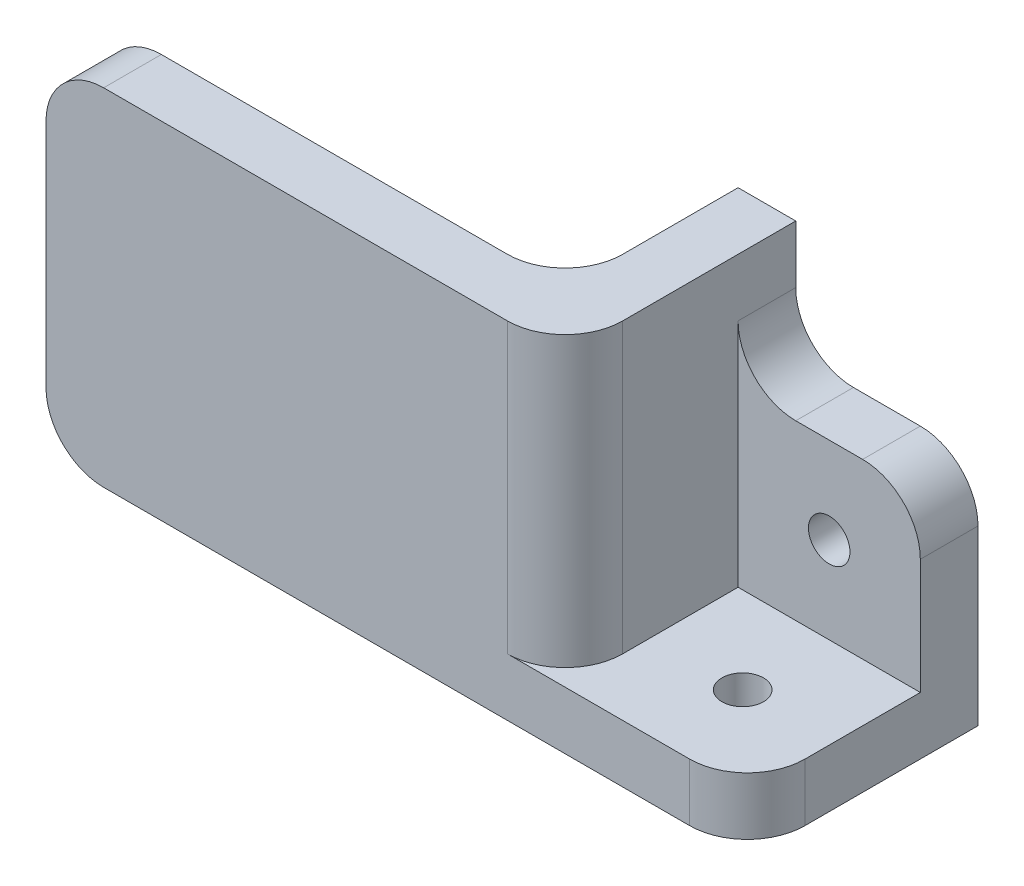
SolidWorks part; units mm, degrees
ref_plane "Front" through (0, 0, 0) normal (0, 0, 1) x (1, 0, 0)
ref_plane "Top" through (0, 0, 0) normal (0, 1, 0) x (1, 0, 0)
ref_plane "Right" through (0, 0, 0) normal (1, 0, 0) x (0, 0, -1)
sketch "Sketch1" plane through (0, 0, 0) normal (0, 1, 0) x (1, 0, 0)
  line L1 (-10.033, -12.7) -> (10.033, -12.7)
  line L2 (-10.033, -12.7) -> (-10.033, 12.7)
  line L3 (-10.033, 12.7) -> (10.033, 12.7)
  line L4 (10.033, -12.7) -> (10.033, 12.7)
  line L5 (-10.033, -12.7) -> (10.033, 12.7) construction
  line L6 (-10.033, 12.7) -> (10.033, -12.7) construction
  point P0 (0, 0)
  dimension "D1" = 20.066
  dimension "D2" = 25.4
extrude "Boss-Extrude1" add sketch "Sketch1" along normal blind 6.35
sketch "Sketch2" plane through (0, 0, -12.7) normal (0, 0, -1) x (-1, 0, 0)
  line L1 (-10.033, 0) -> (10.033, 0)
  line L2 (-10.033, 0) -> (-10.033, 25.4)
  line L3 (-10.033, 25.4) -> (10.033, 25.4)
  line L4 (10.033, 0) -> (10.033, 25.4)
  point P5 (10.033, 0)
  dimension "D1" = 25.4
extrude "Boss-Extrude2" add sketch "Sketch2" against normal blind 6.35
sketch "Sketch3" plane through (-10.033, 0, 0) normal (-1, 0, 0) x (0, 0, 1)
  line L1 (-12.7, 0) -> (12.7, 0)
  line L2 (-12.7, 0) -> (-12.7, 38.1)
  line L3 (-12.7, 38.1) -> (12.7, 38.1)
  line L4 (12.7, 0) -> (12.7, 38.1)
  point P5 (12.7, 0)
  dimension "D1" = 38.1
extrude "Boss-Extrude3" add sketch "Sketch3" along normal blind 6.35
sketch "Sketch4" plane through (0, 0, 12.7) normal (0, 0, 1) x (1, 0, 0)
  line L1 (-16.383, 38.1) -> (-67.183, 38.1)
  line L2 (-16.383, 38.1) -> (-16.383, 0)
  line L3 (-16.383, 0) -> (-67.183, 0)
  line L4 (-67.183, 38.1) -> (-67.183, 0)
  point P5 (-16.383, 0)
  dimension "D1" = 50.8
extrude "Boss-Extrude4" add sketch "Sketch4" against normal blind 6.35
sketch "Sketch6" plane through (0, 0, -6.35) normal (0, 0, 1) x (1, 0, 0)
  line L0 (-10.033, 15.875) -> (10.033, 15.875) construction
  line L1 (-10.033, 6.35) -> (-10.033, 25.4) construction
  line L2 (10.033, 25.4) -> (10.033, 6.35) construction
  circle A0 centre (0, 15.875) radius 2.286
  dimension "D1" = 4.572
extrude "Cut-Extrude1" cut sketch "Sketch6" against normal through all
sketch "Sketch7" plane through (0, 6.35, 0) normal (0, 1, 0) x (1, 0, 0)
  line L0 (10.033, -3.175) -> (-10.033, -3.175) construction
  line L1 (10.033, -12.7) -> (10.033, 6.35) construction
  line L2 (-10.033, 6.35) -> (-10.033, -12.7) construction
  circle A0 centre (0, -3.175) radius 2.286
  dimension "D1" = 4.572
extrude "Cut-Extrude2" cut sketch "Sketch7" against normal through all
fillet "Fillet1" radius 6.35 7 edges at (-16.383, 19.05, 6.35) (-10.033, 22.225, 12.7) (-10.033, 25.4, -9.525) (10.033, 25.4, -9.525) (10.033, 3.175, 12.7) (-67.183, 0, 9.525) (-67.183, 38.1, 9.525)
